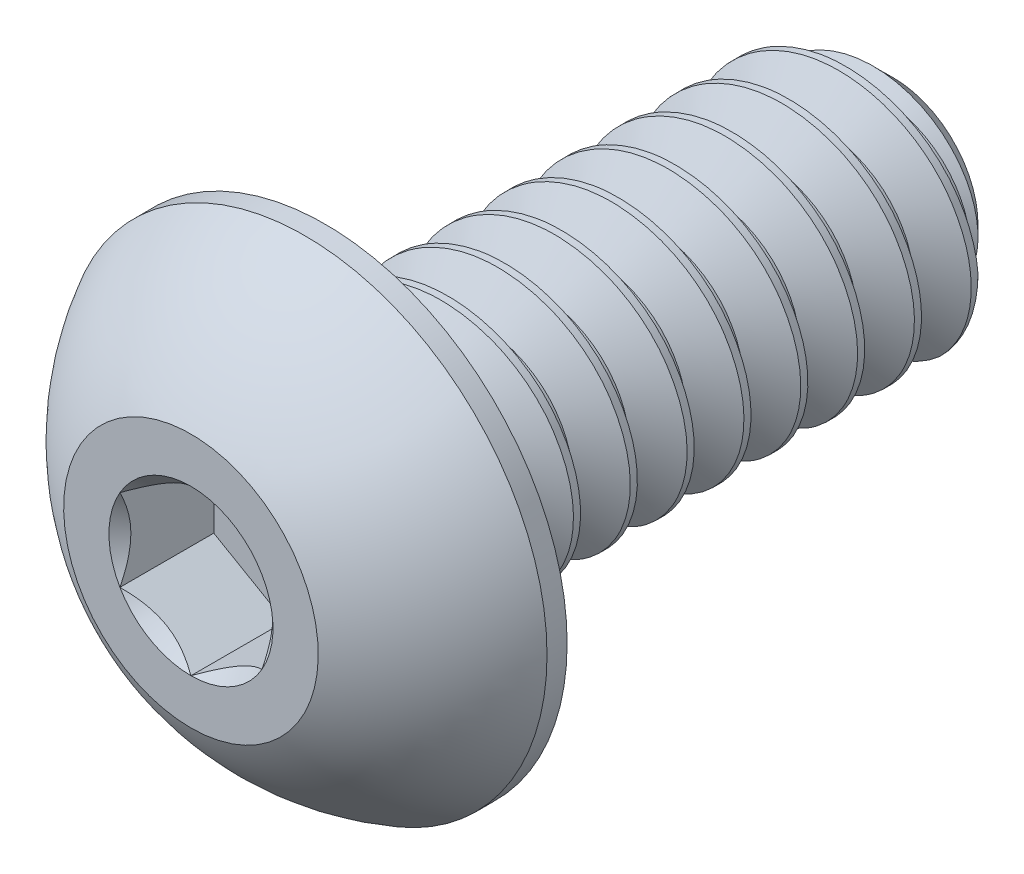
SolidWorks part; units mm, degrees
ref_plane "Front" through (0, 0, 0) normal (0, 0, 1) x (1, 0, 0)
ref_plane "Top" through (0, 0, 0) normal (0, 1, 0) x (1, 0, 0)
ref_plane "Right" through (0, 0, 0) normal (1, 0, 0) x (0, 0, -1)
sketch "Sketch1" plane through (0, 0, 0) normal (1, 0, 0) x (0, 0, -1)
  line L2 (1.4986, 1.4224) -> (7.8486, 1.4224)
  line L3 (7.8486, 1.4224) -> (7.8486, 0)
  line L4 (7.8486, 0) -> (1.4986, 0)
  line L6 (1.2738, 2.7051) -> (1.4986, 2.7051) construction
  line L7 (7.8486, 1.4224) -> (7.8486, -1.4224) construction
  line L8 (0, 0) -> (1.4986, 0) construction
  line L9 (1.4986, 2.7051) -> (1.4986, -2.7051) construction
  line L11 (1.4986, 1.4224) -> (1.4986, 0)
  line L13 (0, 0.7937) -> (0, -0.7937) construction
  line L14 (0, 0.7937) -> (0, 1.4224) construction
  arc A3 (0, 1.4224) -> (1.2738, 2.7051) centre (2.7151, 0) cw construction
  dimension "D1" = 0.2248
  dimension "Head Ht" = 1.4986
  dimension "Head Dia" = 5.4102
  dimension "Dia" = 2.8448
  dimension "Lg" = 6.35
  dimension "Hex" = 1.5875
revolve "Revolve1" add sketch "Sketch1" angle 360 about L4
sketch "Sketch3" plane through (0, 0, -7.8486) normal (0, 0, -1) x (-1, 0, 0)
  circle A0 centre (0, 0) radius 1.4224
curve "Helix/Spiral1" pitch 0.635 height 6.985 radius 1.4224 centre (0, 0, -7.8486) axis (0, 0, 1) start towards (0, 1, 0)
sketch "Sketch2" plane through (0, 0, 0) normal (1, 0, 0) x (0, 0, -1)
  line L0 (7.8486, 1.4224) -> (8.4042, 1.4224)
  line L1 (8.4042, 1.4224) -> (8.1661, 1.01)
  line L2 (8.1661, 1.01) -> (8.0867, 1.01)
  line L3 (8.0867, 1.01) -> (7.8486, 1.4224)
  line L4 (7.9677, 1.2162) -> (8.2852, 1.2162) construction
  dimension "D1" = 60
  dimension "D2" = 0.0794
  dimension "D3" = 0.3175
chamfer "Chamfer1" distance 0.4763 angle 45 1 edges at (0, 1.4224, -7.8486)
sweep "Cut-Sweep1" cut profiles "Sketch2" path "Helix/Spiral1"
sketch "Sketch7" plane through (0, 0, 0) normal (1, 0, 0) x (0, 0, -1)
  line L6 (1.2738, 2.7051) -> (1.4986, 2.7051) construction
  line L8 (0, 0) -> (1.4986, 0) construction
  line L11 (1.4986, 2.7051) -> (1.4986, -2.7051) construction
  line L12 (1.2738, 2.7051) -> (1.4986, 2.7051)
  line L13 (0, 0) -> (1.4986, 0)
  line L14 (0, 0.7937) -> (0, -0.7937) construction
  line L15 (1.4986, 2.7051) -> (1.4986, 0)
  line L16 (0, 1.4224) -> (0, 0)
  arc A2 (1.2738, 2.7051) -> (0, 1.4224) centre (2.7151, 0) ccw construction
  arc A3 (1.2738, 2.7051) -> (0, 1.4224) centre (2.7151, 0) ccw
revolve "Revolve2" add sketch "Sketch7" angle 360 about L13
sketch "Sketch5" plane through (0, 0, 0) normal (0, 0, 1) x (1, 0, 0)
  line L1 (0.7937, -0.4583) -> (0.7937, 0.4583)
  line L2 (0.7937, 0.4583) -> (0, 0.9165)
  line L3 (0, 0.9165) -> (-0.7937, 0.4583)
  line L4 (-0.7937, 0.4583) -> (-0.7937, -0.4583)
  line L5 (-0.7937, -0.4583) -> (0, -0.9165)
  line L6 (0, -0.9165) -> (0.7937, -0.4583)
  circle A0 centre (0, 0) radius 0.7937 construction
extrude "Cut-Extrude2" cut sketch "Sketch5" against normal blind 1.049
sketch "Sketch6" plane through (0, 0, 0) normal (0, 0, 1) x (1, 0, 0)
  circle A0 centre (0, 0) radius 0.9165
extrude "Cut-Extrude3" cut sketch "Sketch6" against normal blind 1.049 draft 45
sketch "Sketch9" [suppressed] plane through (0, 0, -1.4986) normal (0, 0, 1) x (1, 0, 0)
  circle A2 centre (0, 0) radius 1.4224
extrude "Boss-Extrude2" [suppressed] add sketch "Sketch9" against normal offset from surface (12.7 mm away) 31.75 up to face at (0, 0.9461, -7.8486)
sketch "Sketch10" plane through (0, 0, 0) normal (1, 0, 0) x (0, 0, -1)
  line L0 (7.8486, 1.4224) -> (7.8486, -1.4224) construction
  point P0 (6.8961, -1.4224)
  dimension "D1" = 0.9525
equation "\"D3@Helix/Spiral1\" = \"Lg@Sketch1\" + \"D4@Helix/Spiral1\""
equation "\"D2@Sketch2\" = \"D4@Helix/Spiral1\" * .125"
equation "\"D3@Sketch2\" = \"D4@Helix/Spiral1\" * .5"
equation "\"D1@Chamfer1\" = \"D4@Helix/Spiral1\" * .75"
equation "\"D1@Cut-Extrude2\" = \"Head Ht@Sketch1\" * .7"
equation "\"D1@Sketch1\" = \"Head Ht@Sketch1\" * .15"
equation "\"D1@Sketch10\" = \"D4@Helix/Spiral1\" * 1.5"
equation "\"D1@Cut-Extrude3\" = \"D1@Cut-Extrude2\""
